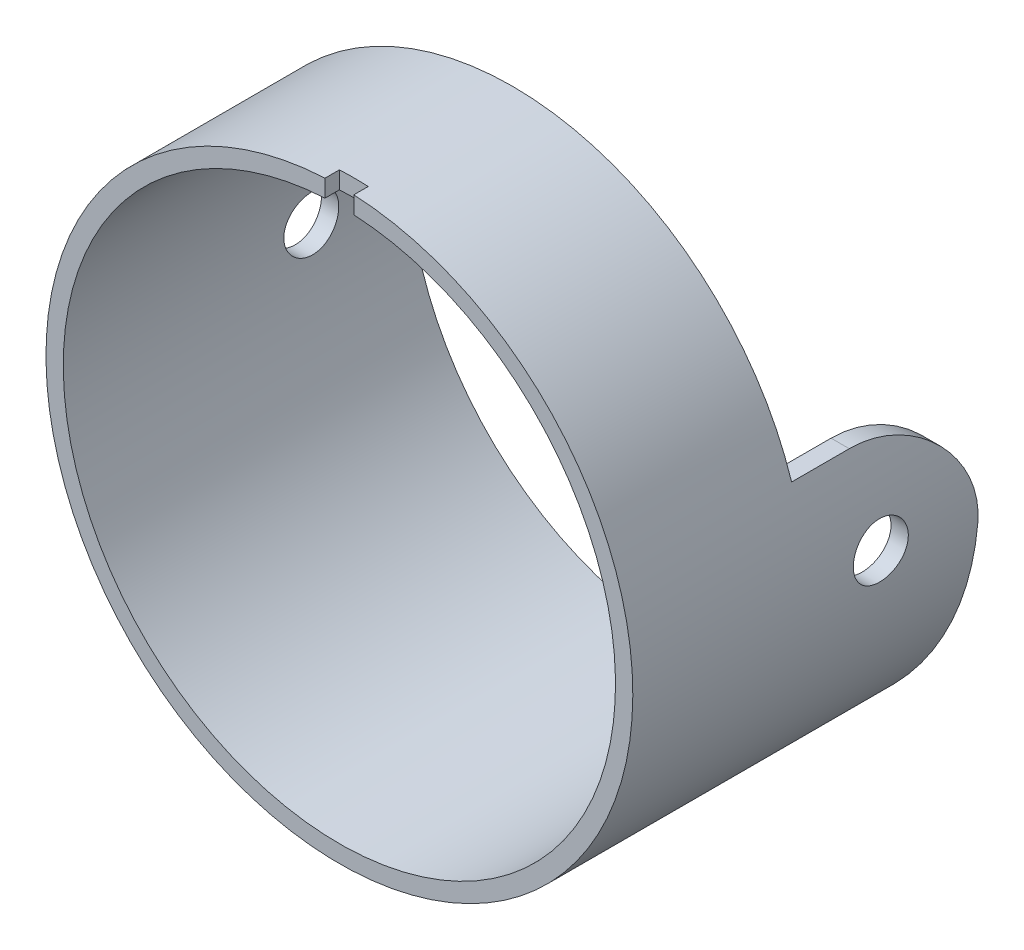
SolidWorks part; units mm, degrees
ref_plane "Front Plane" through (0, 0, 0) normal (0, 0, 1) x (1, 0, 0)
ref_plane "Top Plane" through (0, 0, 0) normal (0, 1, 0) x (1, 0, 0)
ref_plane "Right Plane" through (0, 0, 0) normal (1, 0, 0) x (0, 0, -1)
sketch "Sketch2" plane through (0, 0, 0) normal (0, 0, 1) x (1, 0, 0)
  circle A0 centre (0, 0) radius 47.875
  circle A1 centre (0, 0) radius 50.875
  dimension "D1" = 95.75
  dimension "D2" = 3
extrude "Boss-Extrude1" add sketch "Sketch2" along normal blind 60
sketch "Sketch3" plane through (0, 0, 0) normal (1, 0, 0) x (0, 0, -1)
  line L0 (-60, 50.875) -> (-60, -50.875)
  line L1 (-60, -50.875) -> (0, -50.875)
  line L2 (0, -50.875) -> (0, 15.6469)
  line L3 (0, -50.875) -> (0, 50.875) construction
  line L4 (0, 15.6469) -> (-30, 15.6469)
  line L5 (-30, 15.6469) -> (-30, 50.875)
  line L6 (0, 50.875) -> (-60, 50.875) construction
  line L7 (-30, 50.875) -> (-60, 50.875)
extrude "Cut-Extrude2" cut sketch "Sketch3" against normal blind 60 and the other way blind 60 flip side to cut
sketch "Sketch4" plane through (0, 0, 0) normal (1, 0, 0) x (0, 0, -1)
  line L0 (0, -50.875) -> (0, 15.6469) construction
  circle A0 centre (-17, 0) radius 4.765
  dimension "D2" = 9.53
  dimension "D1" = 17
extrude "Cut-Extrude3" cut sketch "Sketch4" against normal through all and the other way through all
fillet "Fillet1" radius 20 2 edges at (-46.8275, 15.6469, 0) (46.8275, 15.6469, 0)
sketch "Sketch5" plane through (0, 0, 0) normal (0, 1, 0) x (1, 0, 0)
  line L0 (-50.875, -60) -> (50.875, -60) construction
  line L1 (-2.5, -62.5) -> (2.5, -62.5)
  line L2 (-2.5, -62.5) -> (-2.5, -57.5)
  line L3 (-2.5, -57.5) -> (2.5, -57.5)
  line L4 (2.5, -62.5) -> (2.5, -57.5)
  line L5 (-2.5, -62.5) -> (2.5, -57.5) construction
  line L6 (-2.5, -57.5) -> (2.5, -62.5) construction
  point P0 (0, -60)
  dimension "D1" = 5
  dimension "D2" = 5
extrude "Cut-Extrude4" cut sketch "Sketch5" along normal blind 60
